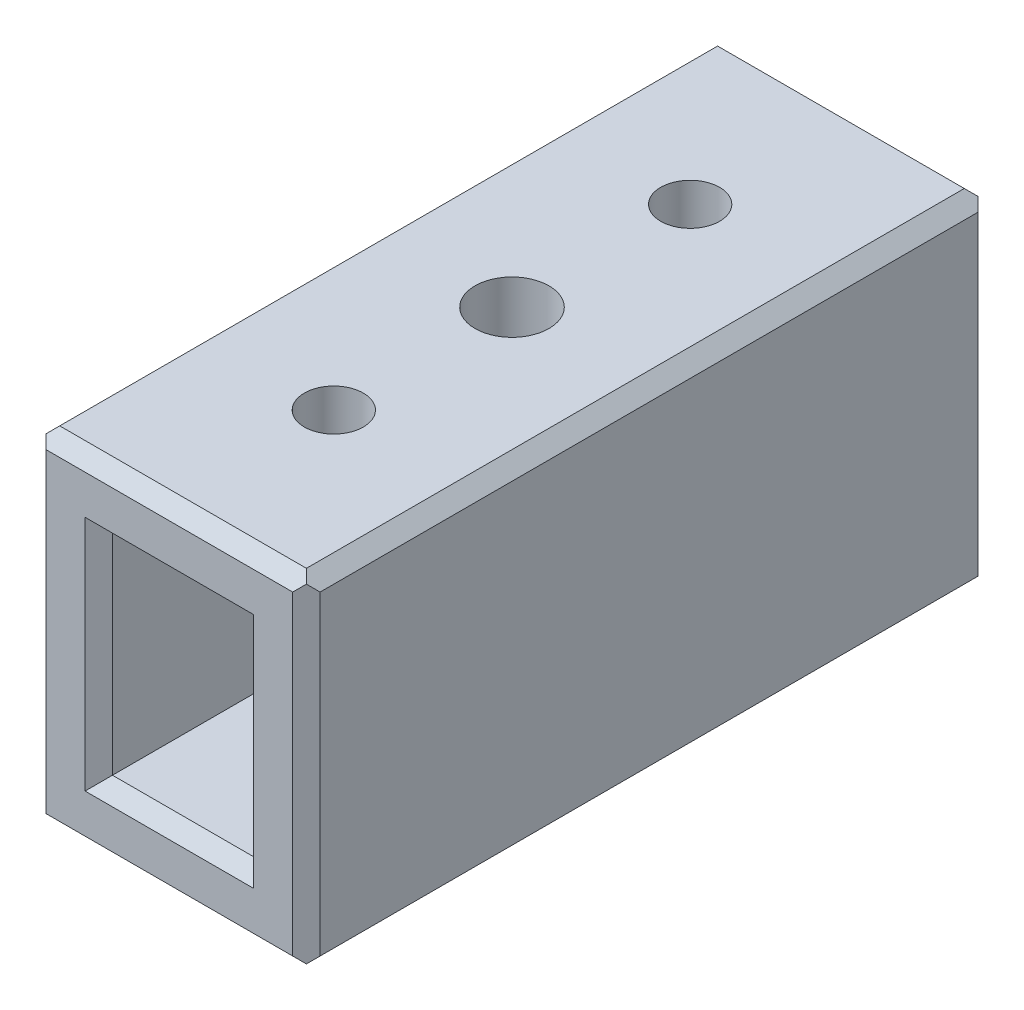
SolidWorks part; units mm, degrees
material "ABS"
ref_plane "前视基准面" through (0, 0, 0) normal (0, 0, 1) x (1, 0, 0)
ref_plane "上视基准面" through (0, 0, 0) normal (0, 1, 0) x (1, 0, 0)
ref_plane "右视基准面" through (0, 0, 0) normal (1, 0, 0) x (0, 0, -1)
other "Configuration Table"
sketch "草图2" plane through (0, 0, 0) normal (0, 0, 1) x (1, 0, 0)
  line L0 (-5.15, 7.65) -> (5.15, 7.65)
  line L1 (-5, 7.5) -> (5, 7.5) construction
  line L2 (-5, 7.5) -> (-5, -7.5) construction
  line L3 (-5, -7.5) -> (5, -7.5) construction
  line L4 (5, 7.5) -> (5, -7.5) construction
  line L5 (0, -7.5) -> (0, 7.5) construction
  line L6 (-5, 0) -> (5, 0) construction
  line L7 (5.15, 7.65) -> (5.15, -7.65)
  line L8 (-5.15, -7.65) -> (5.15, -7.65)
  line L9 (-5.15, 7.65) -> (-5.15, -7.65)
  line L11 (-10, 12.5) -> (10, 12.5)
  line L12 (-10, 12.5) -> (-10, -12.5)
  line L13 (-10, -12.5) -> (10, -12.5)
  line L14 (10, 12.5) -> (10, -12.5)
  line L15 (0, -12.5) -> (0, 12.5) construction
  line L16 (-10, 0) -> (10, 0) construction
  point P0 (0, 0)
  point P11 (0, 0)
  dimension "D1" = 15
  dimension "D2" = 10
  dimension "D4" = 25
  dimension "D5" = 20
  dimension "D3" = 0.15
extrude "凸台-拉伸1" add sketch "草图2" against normal blind 50
sketch "草图3" plane through (0, 12.5, 0) normal (0, 1, 0) x (1, 0, 0)
  line L0 (0, 50) -> (0, 0) construction
  line L1 (0, 12) -> (0, 38) construction
  line L4 (-10, 0) -> (10, 0)
  line L5 (10, 0) -> (10, 50)
  line L6 (10, 50) -> (-10, 50)
  line L7 (-10, 50) -> (-10, 0)
  line L8 (-10, 0) -> (10, 0)
  line L9 (10, 0) -> (10, 50)
  line L10 (10, 50) -> (-10, 50)
  line L11 (-10, 50) -> (-10, 0)
  circle A0 centre (0, 38) radius 2.15
  circle A1 centre (0, 12) radius 2.15
  circle A2 centre (0, 25) radius 2.7
  point P10 (0, 25)
  dimension "D2" = 4.3
  dimension "D3" = 4.3
  dimension "D5" = 5.4
  dimension "D4" = 13
  dimension "D1" = 0
extrude "切除-拉伸2" cut sketch "草图3" against normal through all contours A1 | A2 | A0 region at (0, 12.5, -38) region at (0, 12.5, -12) region at (0, 12.5, -25)
chamfer "倒角1" distance 1 angle 45 16 edges at (0, 12.5, -50) (-10, 0, -50) (0, -12.5, -50) (10, 0, -50) (5.15, 0, -50) (0, -7.65, -50) (-5.15, 0, -50) (0, 7.65, -50) (0, -12.5, 0) (-10, 0, 0) (0, 12.5, 0) (10, 0, 0) (0, -7.65, 0) (5.15, 0, 0) (0, 7.65, 0) (-5.15, 0, 0)
chamfer "倒角2" distance 1 angle 45 4 edges at (10, -12.5, -25) (-10, -12.5, -25) (10, 12.5, -25) (-10, 12.5, -25)
